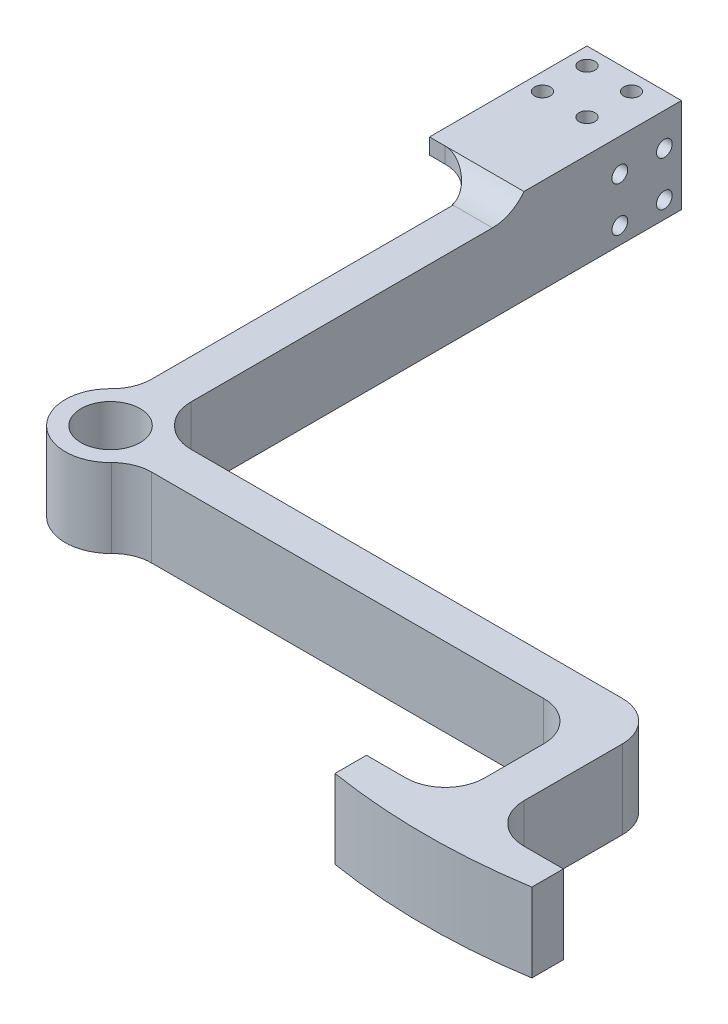
SolidWorks part; units mm, degrees
ref_plane "Front Plane" through (0, 0, 0) normal (0, 0, 1) x (1, 0, 0)
ref_plane "Top Plane" through (0, 0, 0) normal (0, 1, 0) x (1, 0, 0)
ref_plane "Right Plane" through (0, 0, 0) normal (1, 0, 0) x (0, 0, -1)
sketch "Sketch1" plane through (0, 0, 0) normal (0, 1, 0) x (1, 0, 0)
  line L1 (10.3562, 5) -> (135, 5)
  line L2 (10.3562, 5) -> (10.3562, -5)
  line L3 (10.3562, -5) -> (135, -5)
  line L4 (135, 5) -> (135, -5)
  line L10 (-5, 10.3562) -> (5, 10.3562)
  line L11 (-5, 10.3562) -> (-5, 110)
  line L12 (-5, 110) -> (5, 110)
  line L13 (5, 10.3562) -> (5, 110)
  line L15 (5, 110) -> (1, 110)
  line L16 (5, 110) -> (5, 140)
  line L17 (5, 140) -> (1, 140)
  line L18 (1, 110) -> (1, 140)
  line L20 (135, -5) -> (125, -5)
  line L21 (135, -5) -> (135, -50)
  line L22 (135, -50) -> (125, -50)
  line L23 (125, -5) -> (125, -50)
  line L24 (105, -50) -> (155, -50)
  line L25 (105, -50) -> (105, -40)
  line L26 (105, -40) -> (155, -40)
  line L27 (155, -50) -> (155, -40)
  circle A0 centre (0, 0) radius 7.5
  circle A1 centre (0, 0) radius 11.5
  arc A2 (105, -48) -> (155, -48) centre (130, 107.25) ccw
  point P9 (10.3562, 0)
  point P17 (0, 10.3562)
  point P26 (130, -50)
  point P27 (130, -50)
  dimension "D1" = 15
  dimension "D3" = 10
  dimension "D4" = 10
  dimension "D5" = 130
  dimension "D6" = 50
  dimension "D7" = 10
  dimension "D8" = 110
  dimension "D9" = 30
  dimension "D10" = 4
  dimension "D11" = 50
  dimension "D12" = 10
  dimension "D13" = 2
  dimension "D14" = 2
  dimension "D2" = 4
extrude "Boss-Extrude1" add sketch "Sketch1" along normal blind 20 contours L25 A2 L23 L26 | A2 L21 L26 L23 | L21 A2 L27 L26 | L23 L26 L21 L3 | L2 A1 L10 A0 | L18 L12 L16 L17 | L4 L1 L2 L3 | L12 L11 L10 L13 region at (10.0471, 0, 0) region at (130, 0, 22.5) region at (3, 0, -125) region at (144.6514, 0, 44.6049) region at (130, 0, 44.9868) region at (115.3486, 0, 44.6049)
sketch "Sketch2" plane through (5, 0, 0) normal (1, 0, 0) x (0, 0, -1)
  line L0 (140, 20) -> (140, 0) construction
  line L1 (130, 10) -> (130, 0) construction
  line L4 (130, 10) -> (140, 10) construction
  line L5 (10.3562, 0) -> (140, 0) construction
  circle A0 centre (130, 10) radius 8 construction
  circle A1 centre (135.6569, 4.3431) radius 2
  circle A2 centre (124.3431, 4.3431) radius 2
  circle A3 centre (124.3431, 15.6569) radius 2
  circle A4 centre (135.6569, 15.6569) radius 2
  point P5 (140, 10)
  dimension "D1" = 16
  dimension "D2" = 4
  dimension "D3" = 4
extrude "Cut-Extrude1" cut sketch "Sketch2" against normal up to next
fillet "Fillet1" radius 10 9 edges at (1, 10, -110) (125, 10, 40) (135, 10, 40) (125, 10, 5) (135, 10, -5) (10.3562, 10, 5) (10.3562, 10, -5) (5, 10, -10.3562) (-5, 10, -10.3562)
sketch "Sketch3" plane through (5, 0, 0) normal (1, 0, 0) x (0, 0, -1)
  line L1 (140, 20) -> (100, 20)
  line L2 (140, 20) -> (140, 24)
  line L3 (140, 24) -> (100, 24)
  line L4 (140, 20) -> (15.4029, 20)
  line L5 (15.4029, 20) -> (15.4029, 0)
  line L6 (15.4029, 0) -> (140, 0)
  line L7 (140, 0) -> (140, 20)
  line L8 (140, 20) -> (15.4029, 20)
  line L9 (15.4029, 20) -> (15.4029, 0)
  line L10 (15.4029, 0) -> (140, 0)
  line L11 (140, 0) -> (140, 20)
  line L12 (100, 20) -> (100, 24)
  line M11 (140, 20) -> (15.4029, 20)
  dimension "D2" = 40
  dimension "D3" = 4
  dimension "D1" = 0
extrude "Boss-Extrude2" add sketch "Sketch3" against normal blind 24 contours L12 L2 L3 M11 region at (5, 22, -120)
sketch "Sketch4" plane through (0, 24, 0) normal (0, 1, 0) x (1, 0, 0)
  line L0 (-9, 130) -> (-9, 140) construction
  line L1 (-9, 130) -> (1, 130) construction
  line L4 (1, 119.1652) -> (1, 140) construction
  line L5 (1, 119.1652) -> (1, 140)
  line L6 (-19, 140) -> (1, 140) construction
  line L7 (-19, 140) -> (1, 140)
  line L8 (-3.3431, 135.6569) -> (-14.6569, 124.3431) construction
  line L9 (-3.3431, 124.3431) -> (-14.6569, 135.6569) construction
  circle A0 centre (-9, 130) radius 8 construction
  circle A1 centre (-3.3431, 124.3431) radius 2
  circle A2 centre (-14.6569, 124.3431) radius 2
  circle A3 centre (-14.6569, 135.6569) radius 2
  circle A4 centre (-3.3431, 135.6569) radius 2
  point P32 (-9, 140)
  dimension "D1" = 16
  dimension "D2" = 4
  dimension "D3" = 4
  dimension "D4" = 4
  dimension "D5" = 4
extrude "Cut-Extrude2" cut sketch "Sketch4" against normal up to next contours A4 | A3 | A2 | A1 region at (-3.3431, 24, -124.3431) region at (-14.6569, 24, -124.3431) region at (-14.6569, 24, -135.6569) region at (-3.3431, 24, -135.6569)
fillet "Fillet3" radius 10 1 edges at (0, 20, -100)
fillet "Fillet4" radius 10 1 edges at (-5, 22, -100)
